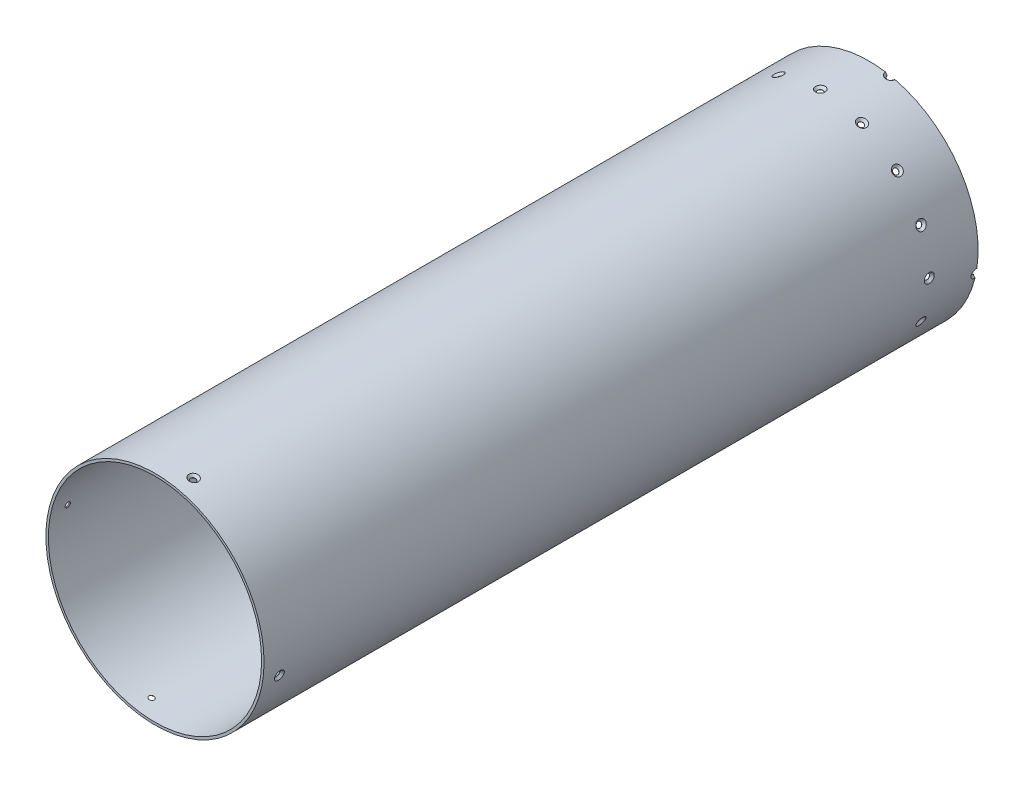
SolidWorks part; units mm, degrees
material "6061-T6 (SS)"
ref_plane "Front Plane" through (0, 0, 0) normal (0, 0, 1) x (1, 0, 0)
ref_plane "Top Plane" through (0, 0, 0) normal (0, 1, 0) x (1, 0, 0)
ref_plane "Right Plane" through (0, 0, 0) normal (1, 0, 0) x (0, 0, -1)
sketch "Sketch1" plane through (0, 0, 0) normal (0, 0, 1) x (1, 0, 0)
  circle A0 centre (0, 0) radius 69.85
  circle A1 centre (0, 0) radius 68.2625
  dimension "D1" = 139.7
  dimension "D2" = 1.5875
extrude "Extrude1" add sketch "Sketch1" along normal blind 457.2
ref_plane "Plane1" through (0, 0, 31.242) normal (0, 0, -1) x (-1, 0, 0)
sketch "Sketch2" plane through (0, 0, 31.242) normal (0, 0, -1) x (-1, 0, 0)
  line L0 (0, 0) -> (0, -69.85) construction
  line L1 (0, 0) -> (-13.6271, -68.5079) construction
  circle A0 centre (0, 0) radius 69.85 construction
  circle A1 centre (0, 0) radius 69.85 construction
  dimension "D1" = 11.25
ref_plane "Plane2" through (0, -69.85, 31.242) normal (0, -1, 0) x (1, 0, 0)
hole_wizard "CSK for M3 Flat Head Machine Screw1" positions "Sketch5" profile "Sketch4" countersink size "M3" standard "Ansi Metric" end condition through all
sketch "Sketch5" plane through (0, -69.85, 31.242) normal (0, -1, 0) x (1, 0, 0)
  point P2 (0, 0)
sketch "Sketch4" plane through (0, -69.85, 31.242) normal (1, 0, 0) x (0, 0, -1)
  line L0 (0, 0) -> (0, 161.1134)
  line L1 (0, 161.1134) -> (1.7, 161.1134)
  line L2 (1.7, 161.1134) -> (1.7, 1.45)
  line L3 (1.7, 1.45) -> (3.15, 0)
  line L5 (3.15, 0) -> (0, 0)
  line L6 (-1.7, 1.45) -> (-3.15, 0) construction
  line L11 (0, -6.35) -> (0, 107.95) construction
  dimension "Thru Hole Dia." = 3.4
  dimension "Thru Hole Depth" = 161.1134
  dimension "Near C'Sink Dia." = 6.3
  dimension "Near C'Sink Angle" = 90
pattern_circular "CirPattern1" count 16 over 360 about axis through (0, 0, 457.2) along (0, 0, -1) of "CSK for M3 Flat Head Machine Screw1"
ref_plane "Plane3" through (0, 0, 446.0875) normal (0, 0, 1) x (1, 0, 0)
ref_plane "Plane5" through (0, 0, 0) normal (0.8315, 0.5556, 0) x (-0.5556, 0.8315, 0)
ref_plane "Plane7" through (0, 0, 0) normal (0.5556, -0.8315, 0) x (0.8315, 0.5556, 0)
ref_plane "Plane9" through (0, 0, 0) normal (-0.1951, -0.9808, 0) x (0.9808, -0.1951, 0)
sketch "Sketch7" plane through (0, 0, 457.2) normal (0, 0, 1) x (1, 0, 0)
  circle A0 centre (0, 0) radius 69.85 construction
  point P0 (69.85, 0)
ref_plane "Plane10" through (13.6271, -68.5079, 31.242) normal (0.1951, -0.9808, 0) x (0.9808, 0.1951, 0)
hole_wizard "#10 Clearance Hole1" positions "Sketch12" profile "Sketch11" hole size "#10" standard "Ansi Inch"
sketch "Sketch12" plane through (13.6271, -68.5079, 31.242) normal (0.1951, -0.9808, 0) x (0.9808, 0.1951, 0)
  point P1 (0, 0)
sketch "Sketch11" plane through (13.6271, -68.5079, 31.242) normal (0, 0, 1) x (0.9808, 0.1951, 0)
  line L0 (0, 0) -> (0, 14.2338)
  line L1 (0, 14.2338) -> (2.5527, 12.7)
  line L2 (2.5527, 12.7) -> (2.5527, 0)
  line L5 (2.5527, 0) -> (0, 0)
  line L10 (0, 14.2338) -> (-2.5527, 12.7) construction
  line L11 (0, -6.35) -> (0, 107.95) construction
  dimension "Hole Dia." = 5.1054
  dimension "Hole Depth" = 12.7
  dimension "Drill Angle" = 118
sketch "Sketch13" plane through (13.6271, -68.5079, 31.242) normal (0.1951, -0.9808, 0) x (0.9808, 0.1951, 0)
  line L0 (0, 0) -> (0, 20.3882) construction
ref_plane "Plane11" through (0, 0, 0) normal (0.9808, 0.1951, 0) x (0, 0, -1)
ref_plane "Plane12" through (0, 0, 446.0748) normal (0, 0, 1) x (1, 0, 0)
sketch "Sketch15" plane through (0, 0, 446.0748) normal (0, 0, 1) x (1, 0, 0)
  line L0 (0, 0) -> (13.6271, 68.5079) construction
  line L2 (0, 0) -> (0, 70.1529) construction
  line L3 (0, 69.8152) -> (0, 68.4) construction
  circle A1 centre (0, 0) radius 69.85 construction
  dimension "D1" = 11.25
ref_plane "Plane13" through (13.6271, 68.5079, 446.0748) normal (0.1951, 0.9808, 0) x (-0.9808, 0.1951, 0)
hole_wizard "CSK for M3 Flat Head Machine Screw2" positions "Sketch17" profile "Sketch16" countersink size "M3" standard "Ansi Metric"
sketch "Sketch17" plane through (13.6271, 68.5079, 446.0748) normal (0.1951, 0.9808, 0) x (-0.9808, 0.1951, 0)
  point P0 (0, -446.0748)
  point P7 (0, 0)
sketch "Sketch16" plane through (13.6271, 68.5079, 0) normal (0, 0, 1) x (-0.9808, 0.1951, 0)
  line L0 (0, 0) -> (0, 8.6415)
  line L1 (0, 8.6415) -> (1.7, 7.62)
  line L2 (1.7, 7.62) -> (1.7, 1.45)
  line L3 (1.7, 1.45) -> (3.15, 0)
  line L5 (3.15, 0) -> (0, 0)
  line L6 (-1.7, 1.45) -> (-3.15, 0) construction
  line L10 (0, 8.6415) -> (-1.7, 7.62) construction
  line L11 (0, -6.35) -> (0, 107.95) construction
  dimension "Hole Dia." = 3.4
  dimension "Hole Depth" = 7.62
  dimension "Near C'Sink Dia." = 6.3
  dimension "Near C'Sink Angle" = 90
  dimension "Drill Angle" = 118
pattern_circular "CirPattern2" count 4 over 360 about axis through (0, 0, 457.2) along (0, 0, -1) of "CSK for M3 Flat Head Machine Screw2"
